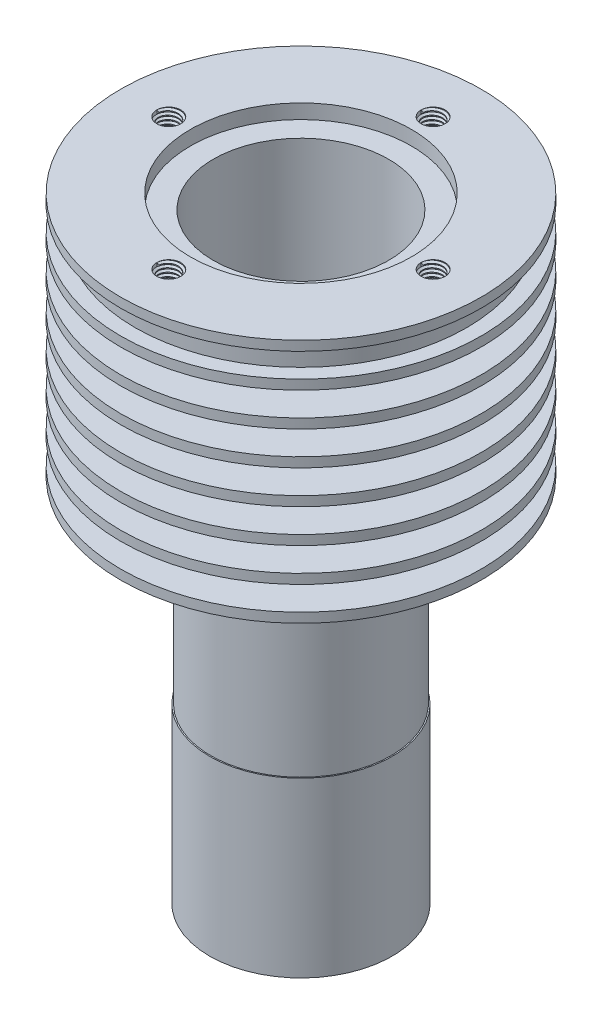
SolidWorks part; units mm, degrees
ref_plane "Front Plane" through (0, 0, 0) normal (0, 0, 1) x (1, 0, 0)
ref_plane "Top Plane" through (0, 0, 0) normal (0, 1, 0) x (1, 0, 0)
ref_plane "Right Plane" through (0, 0, 0) normal (1, 0, 0) x (0, 0, -1)
sketch "Sketch1" plane through (0, 0, 0) normal (0, 1, 0) x (1, 0, 0)
  circle A0 centre (0, 0) radius 37.5
  dimension "D1" = 75
extrude "Boss-Extrude1" add sketch "Sketch1" along normal blind 128
sketch "Sketch2" plane through (0, 0, 0) normal (0, -1, 0) x (1, 0, 0)
  circle A0 centre (0, 0) radius 19
  dimension "D1" = 38
extrude "Cut-Extrude1" cut sketch "Sketch2" against normal blind 36 flip side to cut
sketch "Sketch3" plane through (0, 36, 0) normal (0, -1, 0) x (1, 0, 0)
  circle A0 centre (0, 0) radius 18.75
  dimension "D1" = 37.5
extrude "Cut-Extrude2" cut sketch "Sketch3" against normal blind 36 flip side to cut
sketch "Sketch4" plane through (0, 72, 0) normal (0, -1, 0) x (1, 0, 0)
  circle A0 centre (0, 0) radius 19
  dimension "D1" = 38
extrude "Cut-Extrude3" cut sketch "Sketch4" against normal through all flip side to cut
sketch "Sketch5" plane through (0, 0, 0) normal (1, 0, 0) x (0, 0, -1)
  line L1 (37.5, 128) -> (-37.5, 128) construction
  line L5 (-37.5, 128) -> (-37.5, 77) construction
  line L34 (-37.5, 77) -> (-37.5, 79)
  line L36 (-37.5, 84) -> (-37.5, 86)
  line L39 (-37.5, 91) -> (-37.5, 93)
  line L40 (-37.5, 98) -> (-37.5, 100)
  line L43 (-37.5, 105) -> (-37.5, 107)
  line L44 (-37.5, 112) -> (-37.5, 114)
  line L48 (-37.5, 119) -> (-37.5, 121)
  line L49 (-37.5, 121) -> (-34.5, 121)
  line L50 (-34.5, 121) -> (-34.5, 126)
  line L51 (-34.5, 126) -> (-37.5, 126)
  line L54 (-37.5, 128) -> (-37.5, 126)
  line L55 (0, 114) -> (0, 112)
  line L56 (0, 128) -> (0, 119)
  line L57 (-37.5, 98) -> (0, 98)
  line L61 (-37.5, 91) -> (0, 91)
  line L62 (-37.5, 93) -> (0, 93)
  line L63 (-37.5, 84) -> (0, 84)
  line L64 (-37.5, 86) -> (0, 86)
  line L65 (-37.5, 77) -> (0, 77)
  line L66 (-37.5, 79) -> (0, 79)
  line L67 (-37.5, 100) -> (0, 100)
  line L68 (-37.5, 105) -> (0, 105)
  line L69 (-37.5, 107) -> (0, 107)
  line L70 (-37.5, 112) -> (0, 112)
  line L71 (-37.5, 114) -> (0, 114)
  line L72 (-37.5, 119) -> (0, 119)
  line L73 (-37.5, 128) -> (0, 128)
  line L74 (0, 107) -> (0, 105)
  line L75 (0, 100) -> (0, 98)
  line L76 (0, 93) -> (0, 91)
  line L77 (0, 86) -> (0, 84)
  line L78 (0, 79) -> (0, 77)
  point P1 (0, 0)
  dimension "D3" = 2
  dimension "D4" = 2
  dimension "D13" = 3
revolve "Revolve4" add sketch "Sketch5" angle 360 about L78
sketch "Sketch6" plane through (0, 128, 0) normal (0, 1, 0) x (1, 0, 0)
  circle A0 centre (0, 0) radius 23
  dimension "D1" = 46
extrude "Cut-Extrude4" cut sketch "Sketch6" against normal blind 3
sketch "Sketch7" plane through (0, 125, 0) normal (0, 1, 0) x (1, 0, 0)
  circle A0 centre (0, 0) radius 18.25
  dimension "D1" = 36.5
extrude "Cut-Extrude5" cut sketch "Sketch7" against normal through all
sketch "Sketch8" plane through (0, 128, 0) normal (0, 1, 0) x (1, 0, 0)
  circle A1 centre (27.5, 0) radius 2.5
  circle A2 centre (0, 27.5) radius 2.5
  circle A3 centre (-27.5, 0) radius 2.5
  circle A4 centre (0, -27.5) radius 2.5
  dimension "D2" = 5
  dimension "D3" = 5
  dimension "D4" = 5
  dimension "D5" = 5
extrude "Cut-Extrude6" cut sketch "Sketch8" against normal through all
thread "Thread1" pitch 0.8 method extrude profile "Thread Profile1" start angle 0, offset 0, length 8, pitch 0.8, diameter 5
ref_plane "Plane1" through (-2.5, 128, -27.5) normal (0, 0, 1) x (-1, 0, 0)
sketch "Thread Profile1" plane through (-2.5, 128, -27.5) normal (0, 0, 1) x (-1, 0, 0)
  line L0 (0, 0) -> (0, 0.8) construction
  line L11 (0, 0) -> (0, 0.7)
  line L12 (0, 0.7) -> (-0.433, 0.45)
  line L13 (-0.433, 0.45) -> (-0.433, 0.25)
  line L15 (-0.433, 0.25) -> (0, 0)
  line L17 (-0.433, 0.35) -> (0, 0.35) construction
  point P2 (0, 0)
  dimension "Pitch" = 0.8
  dimension "Profile_Angle" = 60
  dimension "Profile_Land" = 0.2
  dimension "Profile_Height" = 0.433
thread "Thread2" pitch 0.8 method extrude profile "Thread Profile2" start angle 0, offset 0, length 8, pitch 0.8, diameter 5
ref_plane "Plane2" through (-2.5, 128, 27.5) normal (0, 0, 1) x (-1, 0, 0)
sketch "Thread Profile2" plane through (-2.5, 128, 27.5) normal (0, 0, 1) x (-1, 0, 0)
  line L0 (0, 0) -> (0, 0.8) construction
  line L11 (0, 0) -> (0, 0.7)
  line L12 (0, 0.7) -> (-0.433, 0.45)
  line L13 (-0.433, 0.45) -> (-0.433, 0.25)
  line L15 (-0.433, 0.25) -> (0, 0)
  line L17 (-0.433, 0.35) -> (0, 0.35) construction
  point P2 (0, 0)
  dimension "Pitch" = 0.8
  dimension "Profile_Angle" = 60
  dimension "Profile_Land" = 0.2
  dimension "Profile_Height" = 0.433
thread "Thread3" pitch 0.8 method extrude profile "Thread Profile3" start angle 0, offset 0, length 8, pitch 0.8, diameter 5
ref_plane "Plane3" through (25, 128, 0) normal (0, 0, 1) x (-1, 0, 0)
sketch "Thread Profile3" plane through (25, 128, 0) normal (0, 0, 1) x (-1, 0, 0)
  line L0 (0, 0) -> (0, 0.8) construction
  line L11 (0, 0) -> (0, 0.7)
  line L12 (0, 0.7) -> (-0.433, 0.45)
  line L13 (-0.433, 0.45) -> (-0.433, 0.25)
  line L15 (-0.433, 0.25) -> (0, 0)
  line L17 (-0.433, 0.35) -> (0, 0.35) construction
  point P2 (0, 0)
  dimension "Pitch" = 0.8
  dimension "Profile_Angle" = 60
  dimension "Profile_Land" = 0.2
  dimension "Profile_Height" = 0.433
thread "Thread4" pitch 0.8 method extrude profile "Thread Profile4" start angle 0, offset 0, length 8, pitch 0.8, diameter 5
ref_plane "Plane4" through (-30, 128, 0) normal (0, 0, 1) x (-1, 0, 0)
sketch "Thread Profile4" plane through (-30, 128, 0) normal (0, 0, 1) x (-1, 0, 0)
  line L0 (0, 0) -> (0, 0.8) construction
  line L11 (0, 0) -> (0, 0.7)
  line L12 (0, 0.7) -> (-0.433, 0.45)
  line L13 (-0.433, 0.45) -> (-0.433, 0.25)
  line L15 (-0.433, 0.25) -> (0, 0)
  line L17 (-0.433, 0.35) -> (0, 0.35) construction
  point P2 (0, 0)
  dimension "Pitch" = 0.8
  dimension "Profile_Angle" = 60
  dimension "Profile_Land" = 0.2
  dimension "Profile_Height" = 0.433
